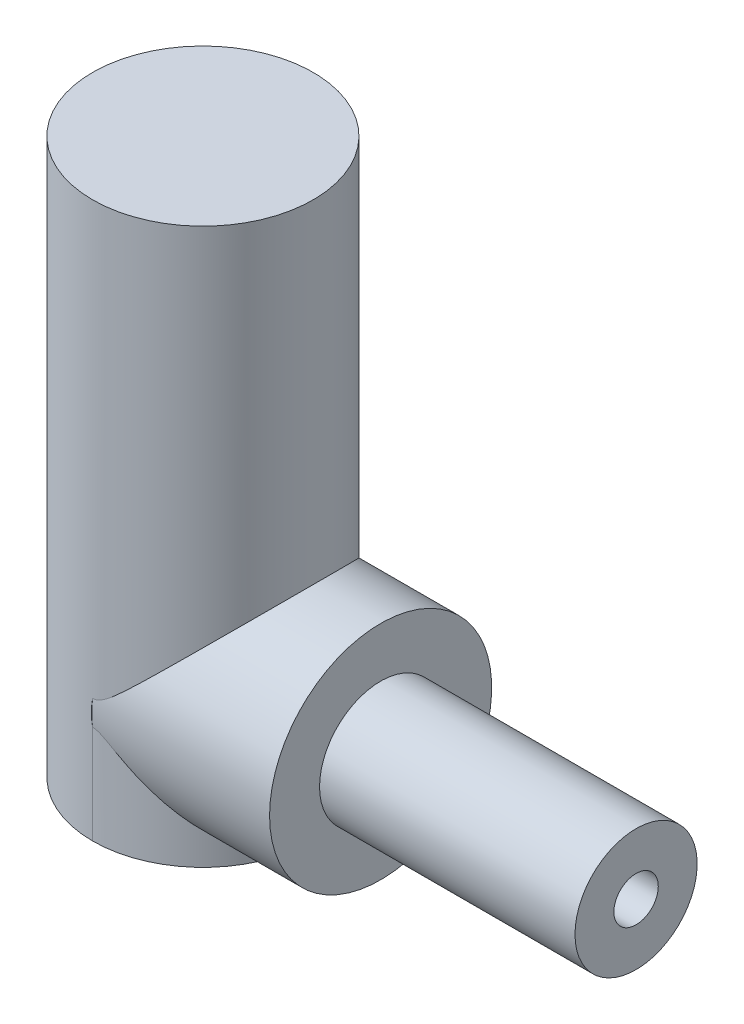
SolidWorks part; units mm, degrees
ref_plane "前视基准面" through (0, 0, 0) normal (0, 0, 1) x (1, 0, 0)
ref_plane "上视基准面" through (0, 0, 0) normal (0, 1, 0) x (1, 0, 0)
ref_plane "右视基准面" through (0, 0, 0) normal (1, 0, 0) x (0, 0, -1)
sketch "草图1" plane through (0, 0, 0) normal (0, 1, 0) x (1, 0, 0)
  line L0 (-52.5974, 0) -> (49.9524, 0) construction
  line L1 (0, 13.0355) -> (0, -15.4504) construction
  line L2 (11.5, 0) -> (11.5, 2.75)
  line L3 (11.5, 2.75) -> (0, 2.75)
  line L4 (0, 2.75) -> (0, 5)
  line L5 (0, 5) -> (-8, 5)
  line L6 (-8, 5) -> (-11, 3.25)
  line L7 (-11, 3.25) -> (-11, 0)
  line L8 (-11, 0) -> (11.5, 0)
  dimension "D1" = 2.75
  dimension "D2" = 11.5
  dimension "D3" = 8
  dimension "D4" = 5
  dimension "D5" = 3
  dimension "D6" = 3.25
revolve "旋转2" add sketch "草图1" angle 360 about L0
sketch "草图2" plane through (11.5, 0, 0) normal (1, 0, 0) x (0, 0, -1)
  circle A0 centre (0, 0) radius 1
  dimension "D1" = 2
extrude "切除-拉伸1" cut sketch "草图2" against normal blind 8
sketch "草图3" plane through (0, 0, 0) normal (0, 1, 0) x (1, 0, 0)
  line L0 (15.8707, 0) -> (-14.4575, 0) construction
  line L1 (-8, -5) -> (-8, 5) construction
  circle A0 centre (-8, 0) radius 4.9681
  point P5 (-8, 0)
extrude "凸台-拉伸1" add sketch "草图3" along normal blind 20 and the other way blind 5
